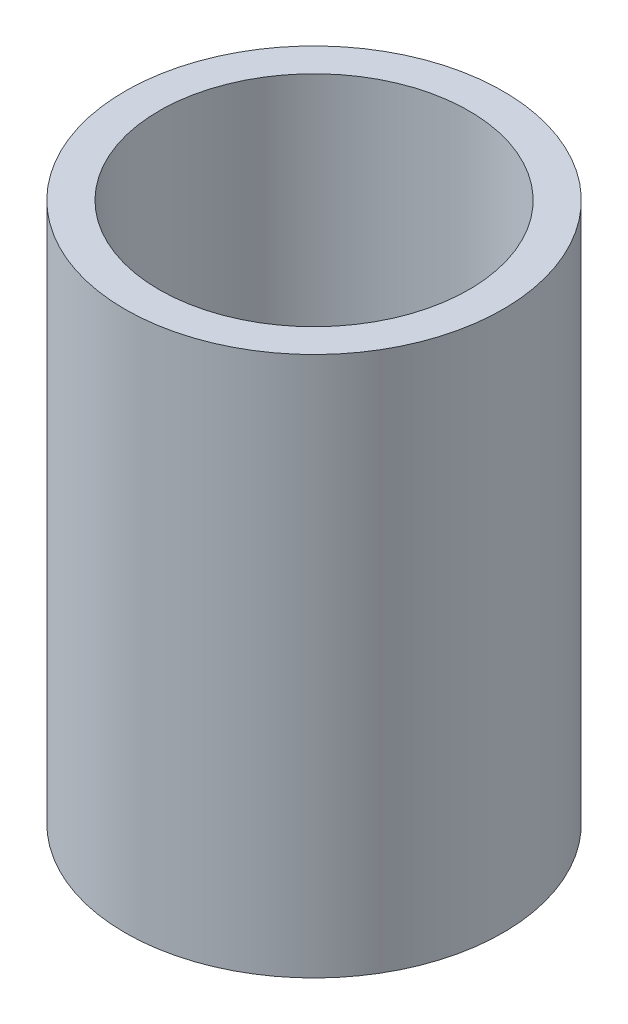
SolidWorks part; units mm, degrees
ref_plane "Front Plane" through (0, 0, 0) normal (0, 0, 1) x (1, 0, 0)
ref_plane "Top Plane" through (0, 0, 0) normal (0, 1, 0) x (1, 0, 0)
ref_plane "Right Plane" through (0, 0, 0) normal (1, 0, 0) x (0, 0, -1)
sketch "Sketch1" plane through (0, 0, 0) normal (0, 1, 0) x (1, 0, 0)
  circle A0 centre (0, 0) radius 60
  dimension "SLEEVE_OD" = 120
extrude "Boss-Extrude1" add sketch "Sketch1" along normal blind 171.4221
sketch "Sketch2" plane through (0, 0, 0) normal (0, 1, 0) x (1, 0, 0)
  circle A0 centre (0, 0) radius 49.187
  dimension "BORE_D" = 98.3739
extrude "Cut-Extrude1" cut sketch "Sketch2" along normal through all
chamfer "Chamfer1" distance 3.7359 angle 62.356 rebuild error yes
